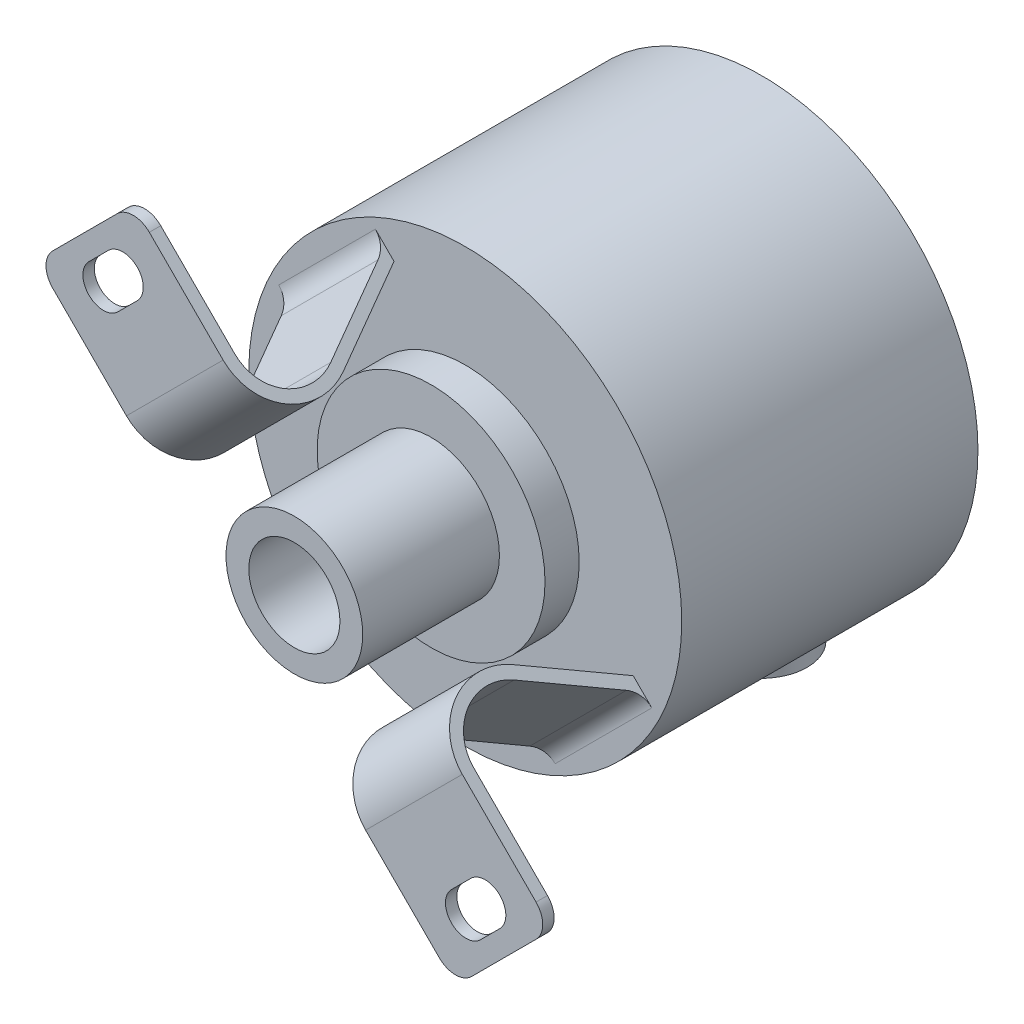
SolidWorks part; units mm, degrees
ref_plane "Front Plane" through (0, 0, 0) normal (0, 0, 1) x (1, 0, 0)
ref_plane "Top Plane" through (0, 0, 0) normal (0, 1, 0) x (1, 0, 0)
ref_plane "Right Plane" through (0, 0, 0) normal (1, 0, 0) x (0, 0, -1)
sketch "Sketch1" plane through (0, 0, 0) normal (0, 0, 1) x (1, 0, 0)
  circle A0 centre (0, 0) radius 19
  dimension "D1" = 38
extrude "Boss-Extrude1" add sketch "Sketch1" along normal blind 26
sketch "Sketch2" plane through (0, 0, 26) normal (0, 0, 1) x (1, 0, 0)
  circle A0 centre (0, 0) radius 10
  dimension "D1" = 20
extrude "Boss-Extrude2" add sketch "Sketch2" along normal blind 3
sketch "Sketch3" plane through (0, 0, 29) normal (0, 0, 1) x (1, 0, 0)
  circle A0 centre (0, 0) radius 6
  dimension "D1" = 12
extrude "Boss-Extrude3" add sketch "Sketch3" along normal blind 12
sketch "Sketch4" plane through (0, 0, 41) normal (0, 0, 1) x (1, 0, 0)
  circle A0 centre (0, 0) radius 4
  dimension "D1" = 8
extrude "Cut-Extrude1" cut sketch "Sketch4" against normal blind 10
sketch "Sketch5" plane through (0, 0, 0) normal (0, 1, 0) x (1, 0, 0)
  circle A0 centre (0, 0) radius 4
  dimension "D1" = 8
extrude "Boss-Extrude4" add sketch "Sketch5" against normal blind 24
fillet "Fillet1" radius 4 1 edges at (0, 0, -4)
ref_axis "Axis1" through (0, 0, -19.546) along (0, 0, 1)
ref_plane "Plane1" through (0, 0, 0) normal (0.7071, 0.7071, 0) x (-0.7071, 0.7071, 0)
sketch "Sketch6" plane through (0, 0, 0) normal (0.7071, 0.7071, 0) x (-0.7071, 0.7071, 0)
  line L0 (-14.8453, 26) -> (-10.5152, 33.5)
  line L1 (19, 26) -> (-19, 26) construction
  line L2 (-14.8453, 41) -> (-26, 41)
  line L3 (0, -19.546) -> (0, 52.4548) construction
  line L4 (-16, 26) -> (-11.3812, 34)
  line L5 (-14.8453, 40) -> (-26, 40)
  line L6 (-15.7113, 26.5) -> (-11.3812, 34) construction
  line L7 (-16, 26) -> (-14.8453, 26)
  line L8 (-26, 41) -> (-26, 40)
  line L9 (-19, 26) -> (-19, 0) construction
  line L10 (0, 0) -> (0, 45.1743) construction
  line L11 (26, 41) -> (26, 40)
  line L12 (16, 26) -> (14.8453, 26)
  line L13 (14.8453, 40) -> (26, 40)
  line L14 (16, 26) -> (11.3812, 34)
  line L15 (14.8453, 41) -> (26, 41)
  line L16 (14.8453, 26) -> (10.5152, 33.5)
  arc A0 (-10.5152, 33.5) -> (-14.8453, 41) centre (-14.8453, 36) ccw
  arc A1 (-11.3812, 34) -> (-14.8453, 40) centre (-14.8453, 36) ccw
  arc A2 (11.3812, 34) -> (14.8453, 40) centre (14.8453, 36) cw
  arc A3 (10.5152, 33.5) -> (14.8453, 41) centre (14.8453, 36) cw
  dimension "D3" = 5
  dimension "D1" = 26
  dimension "D2" = 15
  dimension "D5" = 60
  dimension "D6" = 3
  dimension "D4" = 1
extrude "Boss-Extrude5" add sketch "Sketch6" along normal mid plane 12
sketch "Sketch7" plane through (0, 0, 41) normal (0, 0, 1) x (1, 0, 0)
  line L0 (-18.0312, 16.3342) -> (-16.3342, 18.0312)
  line L1 (-13.7886, 15.4856) -> (-15.4856, 13.7886)
  line L2 (-14.1421, 22.6274) -> (-22.6274, 14.1421) construction
  line L3 (-9.6764, -9.6764) -> (9.6764, 9.6764) construction
  line L4 (-6.2546, 14.7399) -> (-14.7399, 6.2546) construction
  line L5 (-18.0312, 13.7886) -> (-13.7886, 18.0312) construction
  line L6 (-15.9099, 15.9099) -> (15.9099, -15.9099) construction
  line L7 (13.7886, -18.0312) -> (18.0312, -13.7886) construction
  line L8 (15.4856, -13.7886) -> (13.7886, -15.4856)
  line L9 (16.3342, -18.0312) -> (18.0312, -16.3342)
  arc A0 (-13.7886, 15.4856) -> (-16.3342, 18.0312) centre (-15.0614, 16.7584) ccw
  arc A1 (-18.0312, 16.3342) -> (-15.4856, 13.7886) centre (-16.7584, 15.0614) ccw
  arc A2 (16.3342, -18.0312) -> (13.7886, -15.4856) centre (15.0614, -16.7584) cw
  arc A3 (15.4856, -13.7886) -> (18.0312, -16.3342) centre (16.7584, -15.0614) cw
  point P18 (0, 0)
  dimension "D1" = 3.6
  dimension "D2" = 6
  dimension "D3" = 22.5
extrude "Cut-Extrude2" cut sketch "Sketch7" against normal up to next
fillet "Fillet2" radius 2 4 edges at (14.1421, -22.6274, 40.5) (22.6274, -14.1421, 40.5) (-22.6274, 14.1421, 40.5) (-14.1421, 22.6274, 40.5)
fillet "Fillet3" radius 2 2 edges at (-11.3137, 11.3137, 26) (11.3137, -11.3137, 26)
